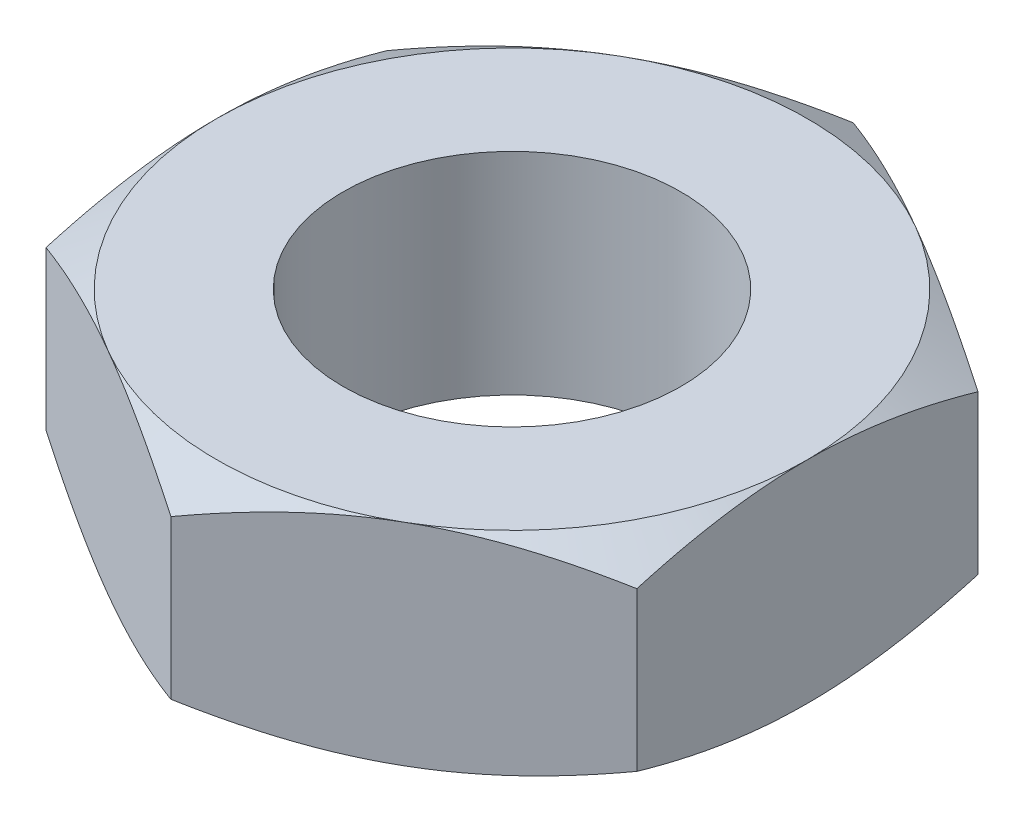
SolidWorks part; units mm, degrees
material "Alloy Steel"
ref_plane "Front Plane" through (0, 0, 0) normal (0, 0, 1) x (1, 0, 0)
ref_plane "Top Plane" through (0, 0, 0) normal (0, 1, 0) x (1, 0, 0)
ref_plane "Right Plane" through (0, 0, 0) normal (1, 0, 0) x (0, 0, -1)
sketch "Sketch1" plane through (0, 0, 0) normal (0, 1, 0) x (1, 0, 0)
  line L1 (-5.5563, 3.2079) -> (-5.5563, -3.2079)
  line L2 (-5.5563, -3.2079) -> (0, -6.4158)
  line L3 (0, -6.4158) -> (5.5562, -3.2079)
  line L4 (5.5562, -3.2079) -> (5.5562, 3.2079)
  line L5 (5.5562, 3.2079) -> (0, 6.4158)
  line L6 (0, 6.4158) -> (-5.5563, 3.2079)
  circle A0 centre (0, 0) radius 5.5563 construction
  circle A1 centre (0, 0) radius 3.175
  dimension "Thread Size" = 6.35
  dimension "Hex" = 11.1125
extrude "Boss-Extrude1" add sketch "Sketch1" along normal mid plane 3.9688
sketch "Sketch2" plane through (0, 1.9844, 0) normal (0, 1, 0) x (1, 0, 0)
  circle A0 centre (0, 0) radius 3.175 construction
  circle A1 centre (0, 0) radius 3.175
curve "Helix/Spiral1" [suppressed] pitch 0.9071 height 4.8759 turns 5.375 parameters "Pitch"=0.9071
sketch "Sketch3" plane through (0, 0, 0) normal (1, 0, 0) x (0, 0, -1)
  line L0 (2.5858, 2.4379) -> (3.175, 2.7781)
  line L1 (3.175, 2.7781) -> (3.175, 1.9844)
  line L2 (3.175, 1.9844) -> (2.5858, 2.3246)
  line L3 (2.5858, 2.3246) -> (2.5858, 2.4379)
  line L4 (2.8804, 2.608) -> (2.8804, 2.1545) construction
  line L5 (2.5858, 2.3812) -> (3.175, 2.3812) construction
  line L6 (3.175, 1.9844) -> (-3.175, 1.9844) construction
  dimension "D1" = 60
  dimension "D2" = 0.1134
  dimension "D3" = 0.4536
sweep "Sweep1" [suppressed] add profiles "Sketch3" path "Helix/Spiral1"
sketch "Sketch4" plane through (0, 1.9844, 0) normal (0, 1, 0) x (1, 0, 0)
  circle A1 centre (0, 0) radius 3.175
  circle A2 centre (0, 0) radius 3.175
  dimension "D1" = 0
extrude "Cut-Extrude1" [suppressed] cut sketch "Sketch4" along normal through all and the other way through all draft 45
sketch "Sketch5" plane through (0, 1.9844, 0) normal (0, 1, 0) x (1, 0, 0)
  circle A0 centre (0, 0) radius 5.5563 construction
  circle A1 centre (0, 0) radius 5.5563
extrude "Cut-Extrude2" cut sketch "Sketch5" against normal through all draft 60 flip side to cut
mirror "Mirror1" about plane through (0, 0, 0) normal (0, 1, 0) of "Cut-Extrude2", "Cut-Extrude1"
equation "\"D2@Sketch3\" = \"Pitch@Helix/Spiral1\"*.125"
equation "\"D3@Sketch3\" = \"Pitch@Helix/Spiral1\"*.5"
equation "\"D3@Helix/Spiral1\" = \"Height@Boss-Extrude1\"+\"Pitch@Helix/Spiral1\""
